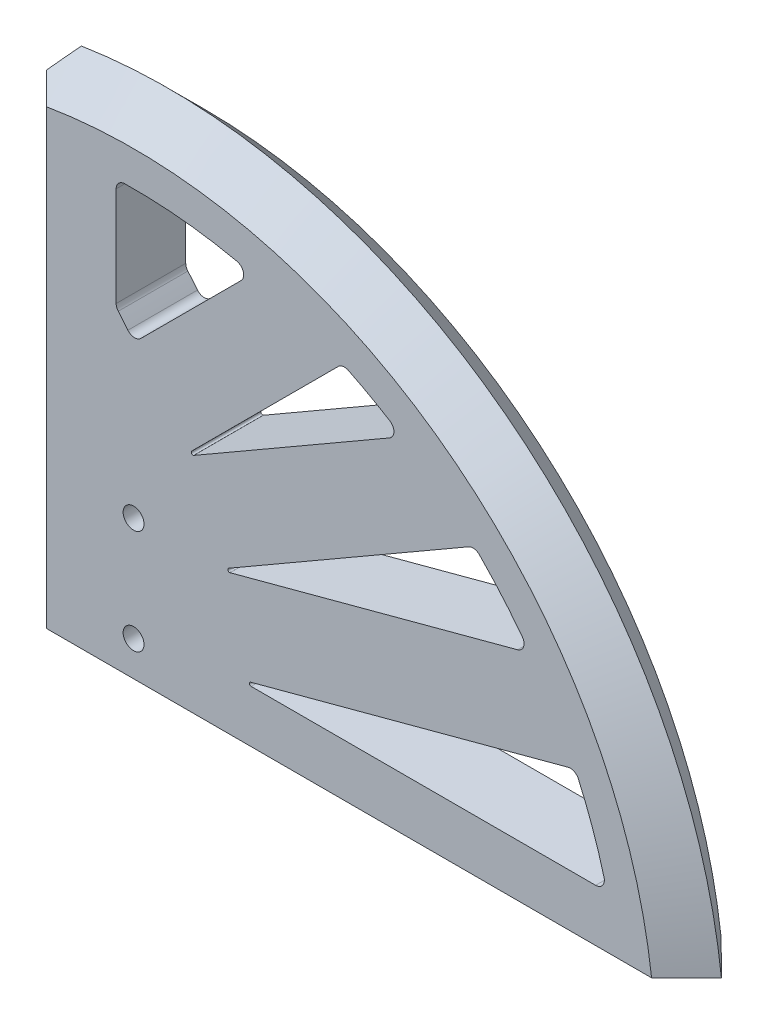
SolidWorks part; units mm, degrees
ref_plane "Front Plane" through (0, 0, 0) normal (0, 0, 1) x (1, 0, 0)
ref_plane "Top Plane" through (0, 0, 0) normal (0, 1, 0) x (1, 0, 0)
ref_plane "Right Plane" through (0, 0, 0) normal (1, 0, 0) x (0, 0, -1)
sketch "Sketch1" plane through (0, 0, 0) normal (0, 0, 1) x (1, 0, 0)
  line L0 (0, 0) -> (0, 27.8325)
  line L1 (0, 0) -> (37.7969, 0)
  line L3 (12, 3) -> (33.211, 3)
  line L6 (5, 18) -> (5, 24.3821)
  line L7 (12, 3) -> (31.3937, 8.1965)
  line L9 (10.8085, 7.8571) -> (28.7851, 12.6739)
  line L12 (10.8085, 7.8571) -> (25.5994, 16.3966)
  line L14 (8.8112, 12.4775) -> (21.4315, 19.7638)
  line L16 (8.8112, 12.4775) -> (18.0217, 21.6879)
  line L17 (12.8195, 23.5568) -> (6.0223, 16.7597)
  circle A2 centre (6, 2) radius 0.6
  circle A3 centre (6, 8) radius 0.6
  arc A17 (0, 27.8325) -> (37.7969, 0) centre (6, -3.6) cw
  arc A24 (5, 24.3821) -> (33.211, 3) centre (6, -3.6) cw
  arc A25 (5, 18) -> (12, 3) centre (-17.6305, -1.6942) cw
  point P36 (0, 0)
  dimension "D4" = 1.2
  dimension "D12" = 6
  dimension "D14" = 32
  dimension "D15" = 5
  dimension "D13" = 12
  dimension "D9" = 3
  dimension "D18" = 30
  dimension "D7" = 28
  dimension "D8" = 30
  dimension "D3" = 2
  dimension "D6" = 6
  dimension "D10" = 3.6
  dimension "D11" = 5
  dimension "D16" = 15
  dimension "D17" = 5
  dimension "D19" = 5
  dimension "D20" = 45
  dimension "20" = 18
  dimension "D5" = 2
extrude "Boss-Extrude1" add sketch "Sketch1" along normal blind 4 contours A17 L0 L1 A25 L6 A24 L3 A3 A2 | L9 A25 L7 A24 | L14 A25 L12 A24 | L6 A25 L16 A24 L17 region at (0.4728, 13.9162, 0) region at (20.8325, 7.9222, 0) region at (16.7737, 14.1119, 0) region at (11.5805, 18.6055, 0)
fillet "Fillet3" radius 0.1 3 edges at (8.8112, 12.4775, 2) (10.8085, 7.8571, 2) (12, 3, 2)
fillet "Fillet4" radius 0.5 10 edges at (33.211, 3, 2) (31.3937, 8.1965, 2) (28.7851, 12.6739, 2) (25.5994, 16.3966, 2) (21.4315, 19.7638, 2) (18.0217, 21.6879, 2) (12.8195, 23.5568, 2) (5, 24.3821, 2) (5, 18, 2) (6.0223, 16.7597, 2)
sketch "Sketch6" plane through (0, 0, 0) normal (0, -1, 0) x (1, 0, 0)
  line L0 (0, 2) -> (37.7969, 2) construction
  line L1 (0, 4) -> (0, 0) construction
  line L2 (37.7969, 4) -> (37.7969, 0) construction
  line L3 (6, 2.75) -> (6, 1.25) construction
  line L4 (8.75, 2.75) -> (3.25, 2.75)
  line L5 (8.75, 2.75) -> (8.75, 1.25)
  line L6 (8.75, 1.25) -> (3.25, 1.25)
  line L7 (3.25, 2.75) -> (3.25, 1.25)
  point P10 (8.75, 2)
  dimension "D1" = 1.5
  dimension "D2" = 6
  dimension "D3" = 5.5
extrude "Cut-Extrude3" cut sketch "Sketch6" against normal blind 12.5
chamfer "Chamfer5" distance 2 angle 45 1 edges at (24.9745, 22.1676, 0)
chamfer "Chamfer6" distance 2 angle 45 1 edges at (24.9745, 22.1676, 4)
chamfer "Chamfer7" distance 3 angle 45 1 edges at (0, 12.8969, 0)
chamfer "Chamfer8" distance 1 angle 45 1 edges at (0, 12.8969, 4)
